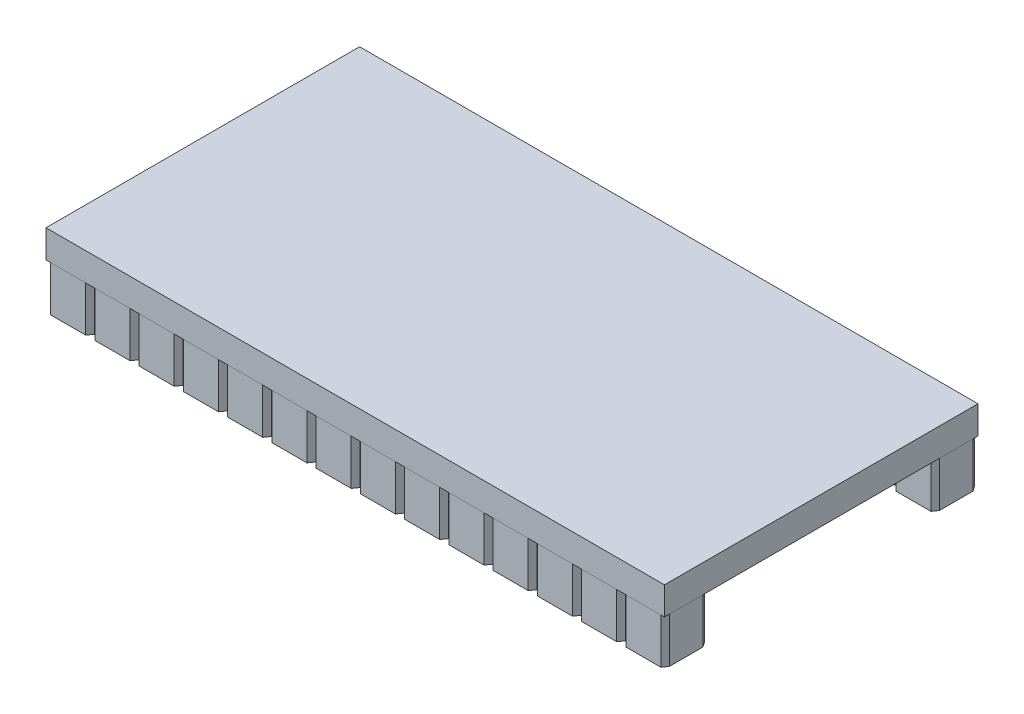
SolidWorks part; units mm, degrees
ref_plane "Front Plane" through (0, 0, 0) normal (0, 0, 1) x (1, 0, 0)
ref_plane "Top Plane" through (0, 0, 0) normal (0, 1, 0) x (1, 0, 0)
ref_plane "Right Plane" through (0, 0, 0) normal (1, 0, 0) x (0, 0, -1)
sketch "Sketch1" plane through (0, 0, 0) normal (0, 1, 0) x (1, 0, 0)
  line L1 (17.75, 9) -> (-17.75, 9)
  line L2 (17.75, 9) -> (17.75, -9)
  line L3 (17.75, -9) -> (-17.75, -9)
  line L4 (-17.75, 9) -> (-17.75, -9)
  line L5 (17.75, 9) -> (-17.75, -9) construction
  line L6 (17.75, -9) -> (-17.75, 9) construction
  point P0 (0, 0)
  dimension "D1" = 18
  dimension "D2" = 35.5
extrude "Boss-Extrude1" add sketch "Sketch1" along normal blind 1.6
sketch "Sketch2" plane through (0, 0, 0) normal (0, -1, 0) x (1, 0, 0)
  line L0 (17.75, 9) -> (17.75, -9) construction
  line L1 (-17.75, 9) -> (17.75, 9)
  line L2 (-17.75, 9) -> (-17.75, 6.5)
  line L3 (-17.75, 6.5) -> (17.75, 6.5)
  line L4 (17.75, 9) -> (17.75, 6.5)
  line L5 (-17.75, 0) -> (17.75, 0) construction
  line L6 (-17.75, -9) -> (-17.75, 9) construction
  line L7 (17.75, -9) -> (17.75, -6.5)
  line L8 (-17.75, -6.5) -> (17.75, -6.5)
  line L9 (-17.75, -9) -> (-17.75, -6.5)
  line L10 (-17.75, -9) -> (17.75, -9)
  dimension "D1" = 2.5
extrude "Boss-Extrude2" add sketch "Sketch2" along normal blind 2.6 separate body
sketch "Sketch3" plane through (0, -2.6, 0) normal (0, -1, 0) x (1, 0, 0)
  line L0 (-18.0101, 9) -> (-17.8, 8.7)
  line L1 (17.75, 9) -> (-17.75, 9) construction
  line L2 (-17.8, 8.7) -> (-17.7, 8.7)
  line L3 (-17.7, 8.7) -> (-17.4899, 9)
  line L4 (-17.4899, 9) -> (-18.0101, 9)
  line L5 (-17.75, 7.75) -> (17.75, 7.75) construction
  line L6 (-17.75, 9) -> (-17.75, 6.5) construction
  line L7 (17.75, 6.5) -> (17.75, 9) construction
  line L8 (-17.75, 0) -> (17.75, 0) construction
  line L9 (-17.75, -9) -> (-17.75, 9) construction
  line L10 (17.75, 9) -> (17.75, -9) construction
  line L11 (-17.75, 8.7) -> (-17.75, 9) construction
  line L12 (-17.7, 6.8) -> (-17.4899, 6.5)
  line L13 (-17.8, 6.8) -> (-17.7, 6.8)
  line L14 (-18.0101, 6.5) -> (-17.8, 6.8)
  line L15 (-17.4899, 6.5) -> (-18.0101, 6.5)
  line L16 (-17.4899, -6.5) -> (-18.0101, -6.5)
  line L17 (-17.7, -6.8) -> (-17.4899, -6.5)
  line L18 (-18.0101, -6.5) -> (-17.8, -6.8)
  line L19 (-17.8, -6.8) -> (-17.7, -6.8)
  line L20 (-17.7, -8.7) -> (-17.4899, -9)
  line L21 (-17.8, -8.7) -> (-17.7, -8.7)
  line L22 (-18.0101, -9) -> (-17.8, -8.7)
  line L23 (-17.4899, -9) -> (-18.0101, -9)
  line L24 (-15.16, -8.7) -> (-14.9499, -9)
  line L25 (-15.26, -8.7) -> (-15.16, -8.7)
  line L26 (-15.4701, -9) -> (-15.26, -8.7)
  line L27 (-14.9499, -9) -> (-15.4701, -9)
  line L28 (-14.9499, -6.5) -> (-15.4701, -6.5)
  line L29 (-15.16, -6.8) -> (-14.9499, -6.5)
  line L30 (-15.4701, -6.5) -> (-15.26, -6.8)
  line L31 (-15.26, -6.8) -> (-15.16, -6.8)
  line L32 (-15.16, 6.8) -> (-14.9499, 6.5)
  line L33 (-15.26, 6.8) -> (-15.16, 6.8)
  line L34 (-15.4701, 6.5) -> (-15.26, 6.8)
  line L35 (-14.9499, 6.5) -> (-15.4701, 6.5)
  line L36 (-14.9499, 9) -> (-15.4701, 9)
  line L37 (-15.4701, 9) -> (-15.26, 8.7)
  line L38 (-15.26, 8.7) -> (-15.16, 8.7)
  line L39 (-15.16, 8.7) -> (-14.9499, 9)
  line L40 (-12.62, -8.7) -> (-12.4099, -9)
  line L41 (-12.72, -8.7) -> (-12.62, -8.7)
  line L42 (-12.9301, -9) -> (-12.72, -8.7)
  line L43 (-12.4099, -9) -> (-12.9301, -9)
  line L44 (-12.4099, -6.5) -> (-12.9301, -6.5)
  line L45 (-12.62, -6.8) -> (-12.4099, -6.5)
  line L46 (-12.9301, -6.5) -> (-12.72, -6.8)
  line L47 (-12.72, -6.8) -> (-12.62, -6.8)
  line L48 (-12.62, 6.8) -> (-12.4099, 6.5)
  line L49 (-12.72, 6.8) -> (-12.62, 6.8)
  line L50 (-12.9301, 6.5) -> (-12.72, 6.8)
  line L51 (-12.4099, 6.5) -> (-12.9301, 6.5)
  line L52 (-12.4099, 9) -> (-12.9301, 9)
  line L53 (-12.9301, 9) -> (-12.72, 8.7)
  line L54 (-12.72, 8.7) -> (-12.62, 8.7)
  line L55 (-12.62, 8.7) -> (-12.4099, 9)
  line L56 (-10.08, -8.7) -> (-9.8699, -9)
  line L57 (-10.18, -8.7) -> (-10.08, -8.7)
  line L58 (-10.3901, -9) -> (-10.18, -8.7)
  line L59 (-9.8699, -9) -> (-10.3901, -9)
  line L60 (-9.8699, -6.5) -> (-10.3901, -6.5)
  line L61 (-10.08, -6.8) -> (-9.8699, -6.5)
  line L62 (-10.3901, -6.5) -> (-10.18, -6.8)
  line L63 (-10.18, -6.8) -> (-10.08, -6.8)
  line L64 (-10.08, 6.8) -> (-9.8699, 6.5)
  line L65 (-10.18, 6.8) -> (-10.08, 6.8)
  line L66 (-10.3901, 6.5) -> (-10.18, 6.8)
  line L67 (-9.8699, 6.5) -> (-10.3901, 6.5)
  line L68 (-9.8699, 9) -> (-10.3901, 9)
  line L69 (-10.3901, 9) -> (-10.18, 8.7)
  line L70 (-10.18, 8.7) -> (-10.08, 8.7)
  line L71 (-10.08, 8.7) -> (-9.8699, 9)
  line L72 (-7.54, -8.7) -> (-7.3299, -9)
  line L73 (-7.64, -8.7) -> (-7.54, -8.7)
  line L74 (-7.8501, -9) -> (-7.64, -8.7)
  line L75 (-7.3299, -9) -> (-7.8501, -9)
  line L76 (-7.3299, -6.5) -> (-7.8501, -6.5)
  line L77 (-7.54, -6.8) -> (-7.3299, -6.5)
  line L78 (-7.8501, -6.5) -> (-7.64, -6.8)
  line L79 (-7.64, -6.8) -> (-7.54, -6.8)
  line L80 (-7.54, 6.8) -> (-7.3299, 6.5)
  line L81 (-7.64, 6.8) -> (-7.54, 6.8)
  line L82 (-7.8501, 6.5) -> (-7.64, 6.8)
  line L83 (-7.3299, 6.5) -> (-7.8501, 6.5)
  line L84 (-7.3299, 9) -> (-7.8501, 9)
  line L85 (-7.8501, 9) -> (-7.64, 8.7)
  line L86 (-7.64, 8.7) -> (-7.54, 8.7)
  line L87 (-7.54, 8.7) -> (-7.3299, 9)
  line L88 (-5, -8.7) -> (-4.7899, -9)
  line L89 (-5.1, -8.7) -> (-5, -8.7)
  line L90 (-5.3101, -9) -> (-5.1, -8.7)
  line L91 (-4.7899, -9) -> (-5.3101, -9)
  line L92 (-4.7899, -6.5) -> (-5.3101, -6.5)
  line L93 (-5, -6.8) -> (-4.7899, -6.5)
  line L94 (-5.3101, -6.5) -> (-5.1, -6.8)
  line L95 (-5.1, -6.8) -> (-5, -6.8)
  line L96 (-5, 6.8) -> (-4.7899, 6.5)
  line L97 (-5.1, 6.8) -> (-5, 6.8)
  line L98 (-5.3101, 6.5) -> (-5.1, 6.8)
  line L99 (-4.7899, 6.5) -> (-5.3101, 6.5)
  line L100 (-4.7899, 9) -> (-5.3101, 9)
  line L101 (-5.3101, 9) -> (-5.1, 8.7)
  line L102 (-5.1, 8.7) -> (-5, 8.7)
  line L103 (-5, 8.7) -> (-4.7899, 9)
  line L104 (-2.46, -8.7) -> (-2.2499, -9)
  line L105 (-2.56, -8.7) -> (-2.46, -8.7)
  line L106 (-2.7701, -9) -> (-2.56, -8.7)
  line L107 (-2.2499, -9) -> (-2.7701, -9)
  line L108 (-2.2499, -6.5) -> (-2.7701, -6.5)
  line L109 (-2.46, -6.8) -> (-2.2499, -6.5)
  line L110 (-2.7701, -6.5) -> (-2.56, -6.8)
  line L111 (-2.56, -6.8) -> (-2.46, -6.8)
  line L112 (-2.46, 6.8) -> (-2.2499, 6.5)
  line L113 (-2.56, 6.8) -> (-2.46, 6.8)
  line L114 (-2.7701, 6.5) -> (-2.56, 6.8)
  line L115 (-2.2499, 6.5) -> (-2.7701, 6.5)
  line L116 (-2.2499, 9) -> (-2.7701, 9)
  line L117 (-2.7701, 9) -> (-2.56, 8.7)
  line L118 (-2.56, 8.7) -> (-2.46, 8.7)
  line L119 (-2.46, 8.7) -> (-2.2499, 9)
  line L120 (0.08, -8.7) -> (0.2901, -9)
  line L121 (-0.02, -8.7) -> (0.08, -8.7)
  line L122 (-0.2301, -9) -> (-0.02, -8.7)
  line L123 (0.2901, -9) -> (-0.2301, -9)
  line L124 (0.2901, -6.5) -> (-0.2301, -6.5)
  line L125 (0.08, -6.8) -> (0.2901, -6.5)
  line L126 (-0.2301, -6.5) -> (-0.02, -6.8)
  line L127 (-0.02, -6.8) -> (0.08, -6.8)
  line L128 (0.08, 6.8) -> (0.2901, 6.5)
  line L129 (-0.02, 6.8) -> (0.08, 6.8)
  line L130 (-0.2301, 6.5) -> (-0.02, 6.8)
  line L131 (0.2901, 6.5) -> (-0.2301, 6.5)
  line L132 (0.2901, 9) -> (-0.2301, 9)
  line L133 (-0.2301, 9) -> (-0.02, 8.7)
  line L134 (-0.02, 8.7) -> (0.08, 8.7)
  line L135 (0.08, 8.7) -> (0.2901, 9)
  line L136 (2.62, -8.7) -> (2.8301, -9)
  line L137 (2.52, -8.7) -> (2.62, -8.7)
  line L138 (2.3099, -9) -> (2.52, -8.7)
  line L139 (2.8301, -9) -> (2.3099, -9)
  line L140 (2.8301, -6.5) -> (2.3099, -6.5)
  line L141 (2.62, -6.8) -> (2.8301, -6.5)
  line L142 (2.3099, -6.5) -> (2.52, -6.8)
  line L143 (2.52, -6.8) -> (2.62, -6.8)
  line L144 (2.62, 6.8) -> (2.8301, 6.5)
  line L145 (2.52, 6.8) -> (2.62, 6.8)
  line L146 (2.3099, 6.5) -> (2.52, 6.8)
  line L147 (2.8301, 6.5) -> (2.3099, 6.5)
  line L148 (2.8301, 9) -> (2.3099, 9)
  line L149 (2.3099, 9) -> (2.52, 8.7)
  line L150 (2.52, 8.7) -> (2.62, 8.7)
  line L151 (2.62, 8.7) -> (2.8301, 9)
  line L152 (5.16, -8.7) -> (5.3701, -9)
  line L153 (5.06, -8.7) -> (5.16, -8.7)
  line L154 (4.8499, -9) -> (5.06, -8.7)
  line L155 (5.3701, -9) -> (4.8499, -9)
  line L156 (5.3701, -6.5) -> (4.8499, -6.5)
  line L157 (5.16, -6.8) -> (5.3701, -6.5)
  line L158 (4.8499, -6.5) -> (5.06, -6.8)
  line L159 (5.06, -6.8) -> (5.16, -6.8)
  line L160 (5.16, 6.8) -> (5.3701, 6.5)
  line L161 (5.06, 6.8) -> (5.16, 6.8)
  line L162 (4.8499, 6.5) -> (5.06, 6.8)
  line L163 (5.3701, 6.5) -> (4.8499, 6.5)
  line L164 (5.3701, 9) -> (4.8499, 9)
  line L165 (4.8499, 9) -> (5.06, 8.7)
  line L166 (5.06, 8.7) -> (5.16, 8.7)
  line L167 (5.16, 8.7) -> (5.3701, 9)
  line L168 (7.7, -8.7) -> (7.9101, -9)
  line L169 (7.6, -8.7) -> (7.7, -8.7)
  line L170 (7.3899, -9) -> (7.6, -8.7)
  line L171 (7.9101, -9) -> (7.3899, -9)
  line L172 (7.9101, -6.5) -> (7.3899, -6.5)
  line L173 (7.7, -6.8) -> (7.9101, -6.5)
  line L174 (7.3899, -6.5) -> (7.6, -6.8)
  line L175 (7.6, -6.8) -> (7.7, -6.8)
  line L176 (7.7, 6.8) -> (7.9101, 6.5)
  line L177 (7.6, 6.8) -> (7.7, 6.8)
  line L178 (7.3899, 6.5) -> (7.6, 6.8)
  line L179 (7.9101, 6.5) -> (7.3899, 6.5)
  line L180 (7.9101, 9) -> (7.3899, 9)
  line L181 (7.3899, 9) -> (7.6, 8.7)
  line L182 (7.6, 8.7) -> (7.7, 8.7)
  line L183 (7.7, 8.7) -> (7.9101, 9)
  line L184 (10.24, -8.7) -> (10.4501, -9)
  line L185 (10.14, -8.7) -> (10.24, -8.7)
  line L186 (9.9299, -9) -> (10.14, -8.7)
  line L187 (10.4501, -9) -> (9.9299, -9)
  line L188 (10.4501, -6.5) -> (9.9299, -6.5)
  line L189 (10.24, -6.8) -> (10.4501, -6.5)
  line L190 (9.9299, -6.5) -> (10.14, -6.8)
  line L191 (10.14, -6.8) -> (10.24, -6.8)
  line L192 (10.24, 6.8) -> (10.4501, 6.5)
  line L193 (10.14, 6.8) -> (10.24, 6.8)
  line L194 (9.9299, 6.5) -> (10.14, 6.8)
  line L195 (10.4501, 6.5) -> (9.9299, 6.5)
  line L196 (10.4501, 9) -> (9.9299, 9)
  line L197 (9.9299, 9) -> (10.14, 8.7)
  line L198 (10.14, 8.7) -> (10.24, 8.7)
  line L199 (10.24, 8.7) -> (10.4501, 9)
  line L200 (12.78, -8.7) -> (12.9901, -9)
  line L201 (12.68, -8.7) -> (12.78, -8.7)
  line L202 (12.4699, -9) -> (12.68, -8.7)
  line L203 (12.9901, -9) -> (12.4699, -9)
  line L204 (12.9901, -6.5) -> (12.4699, -6.5)
  line L205 (12.78, -6.8) -> (12.9901, -6.5)
  line L206 (12.4699, -6.5) -> (12.68, -6.8)
  line L207 (12.68, -6.8) -> (12.78, -6.8)
  line L208 (12.78, 6.8) -> (12.9901, 6.5)
  line L209 (12.68, 6.8) -> (12.78, 6.8)
  line L210 (12.4699, 6.5) -> (12.68, 6.8)
  line L211 (12.9901, 6.5) -> (12.4699, 6.5)
  line L212 (12.9901, 9) -> (12.4699, 9)
  line L213 (12.4699, 9) -> (12.68, 8.7)
  line L214 (12.68, 8.7) -> (12.78, 8.7)
  line L215 (12.78, 8.7) -> (12.9901, 9)
  line L216 (15.32, -8.7) -> (15.5301, -9)
  line L217 (15.22, -8.7) -> (15.32, -8.7)
  line L218 (15.0099, -9) -> (15.22, -8.7)
  line L219 (15.5301, -9) -> (15.0099, -9)
  line L220 (15.5301, -6.5) -> (15.0099, -6.5)
  line L221 (15.32, -6.8) -> (15.5301, -6.5)
  line L222 (15.0099, -6.5) -> (15.22, -6.8)
  line L223 (15.22, -6.8) -> (15.32, -6.8)
  line L224 (15.32, 6.8) -> (15.5301, 6.5)
  line L225 (15.22, 6.8) -> (15.32, 6.8)
  line L226 (15.0099, 6.5) -> (15.22, 6.8)
  line L227 (15.5301, 6.5) -> (15.0099, 6.5)
  line L228 (15.5301, 9) -> (15.0099, 9)
  line L229 (15.0099, 9) -> (15.22, 8.7)
  line L230 (15.22, 8.7) -> (15.32, 8.7)
  line L231 (15.32, 8.7) -> (15.5301, 9)
  line L232 (17.86, -8.7) -> (18.0701, -9)
  line L233 (17.76, -8.7) -> (17.86, -8.7)
  line L234 (17.5499, -9) -> (17.76, -8.7)
  line L235 (18.0701, -9) -> (17.5499, -9)
  line L236 (18.0701, -6.5) -> (17.5499, -6.5)
  line L237 (17.86, -6.8) -> (18.0701, -6.5)
  line L238 (17.5499, -6.5) -> (17.76, -6.8)
  line L239 (17.76, -6.8) -> (17.86, -6.8)
  line L240 (17.86, 6.8) -> (18.0701, 6.5)
  line L241 (17.76, 6.8) -> (17.86, 6.8)
  line L242 (17.5499, 6.5) -> (17.76, 6.8)
  line L243 (18.0701, 6.5) -> (17.5499, 6.5)
  line L244 (18.0701, 9) -> (17.5499, 9)
  line L245 (17.5499, 9) -> (17.76, 8.7)
  line L246 (17.76, 8.7) -> (17.86, 8.7)
  line L247 (17.86, 8.7) -> (18.0701, 9)
  dimension "D1" = 235
  dimension "D2" = 235
  dimension "D3" = 0.3
  dimension "D4" = 15
  dimension "D5" = 0.1
extrude "Cut-Extrude1" cut sketch "Sketch3" against normal up to next (2.6 mm away)
